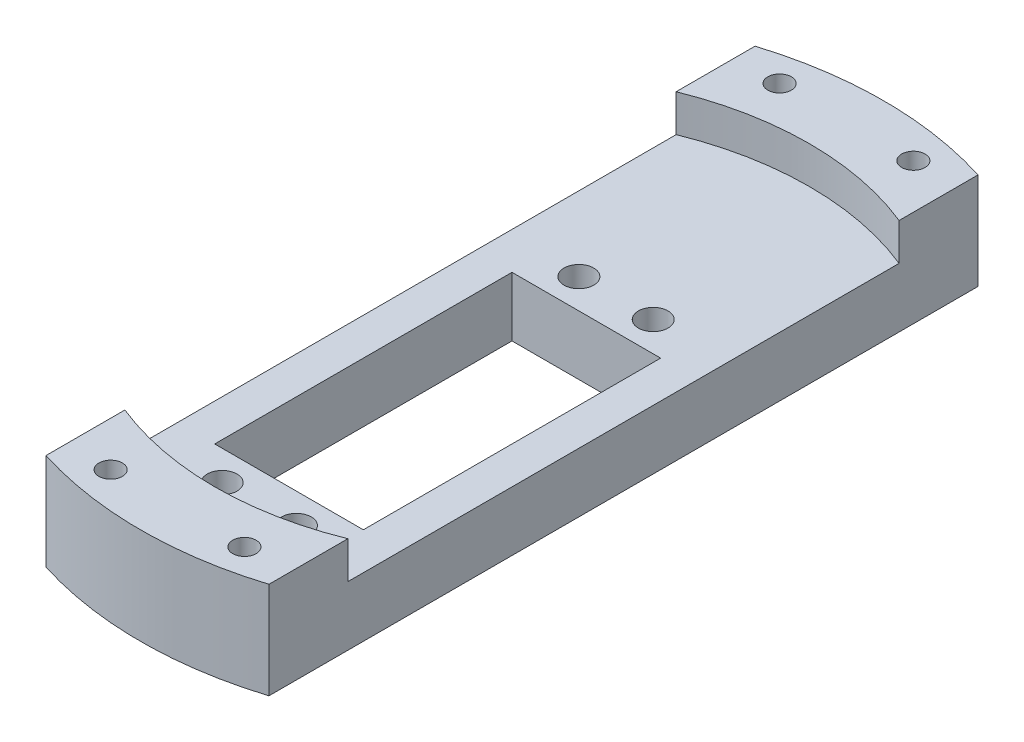
SolidWorks part; units mm, degrees
ref_plane "Спереди" through (0, 0, 0) normal (0, 0, 1) x (1, 0, 0)
ref_plane "Сверху" through (0, 0, 0) normal (0, 1, 0) x (1, 0, 0)
ref_plane "Справа" through (0, 0, 0) normal (1, 0, 0) x (0, 0, -1)
sketch "Эскиз1" plane through (0, 0, 0) normal (0, 1, 0) x (1, 0, 0)
  line L0 (0, 0) -> (0, -69.818) construction
  line L1 (-1000, -10) -> (49000, -10) construction
  line L2 (-10, -30) -> (10, -30)
  line L3 (-10, -30) -> (-10, 10)
  line L4 (-10, 10) -> (10, 10)
  line L5 (10, -30) -> (10, 10)
  line L6 (-10, -30) -> (10, 10) construction
  line L7 (-10, 10) -> (10, -30) construction
  line L8 (-1000, 0) -> (49000, 0) construction
  line L9 (-15, -47.697) -> (-15, 47.697)
  line L10 (15, -47.697) -> (15, 47.697)
  arc A0 (-15, -47.697) -> (15, -47.697) centre (0, 0) ccw
  circle A1 centre (-5, -34) radius 2
  circle A2 centre (5, -34) radius 2
  circle A3 centre (5, 14) radius 2
  circle A4 centre (-5, 14) radius 2
  arc A5 (15, 47.697) -> (-15, 47.697) centre (0, 0) ccw
  point P3 (0, -10)
  dimension "D1" = 100
  dimension "D5" = 4
  dimension "D2" = 10
  dimension "D3" = 40
  dimension "D4" = 20
  dimension "D6" = 24
  dimension "D7" = 5
  dimension "D8" = 15
  dimension "D9" = 15
extrude "Бобышка-Вытянуть1" add sketch "Эскиз1" along normal blind 8
sketch "Эскиз2" plane through (0, 8, 0) normal (0, 1, 0) x (1, 0, 0)
  line L0 (-15, 37.081) -> (-15, 47.697)
  line L1 (-15, 47.697) -> (-15, -47.697) construction
  line L2 (15, 47.697) -> (15, 37.081)
  line L3 (15, -47.697) -> (15, 47.697) construction
  line L4 (-15, -37.081) -> (-15, -47.697)
  line L5 (15, -37.081) -> (15, -47.697)
  arc A0 (-15, -47.697) -> (15, -47.697) centre (0, 0) ccw
  arc A1 (-15, -37.081) -> (15, -37.081) centre (0, 0) ccw
  arc A2 (15, 37.081) -> (-15, 37.081) centre (0, 0) ccw
  arc A3 (15, 47.697) -> (-15, 47.697) centre (0, 0) ccw
  dimension "D1" = 30
  dimension "D2" = 80
  dimension "D3" = 50
extrude "Бобышка-Вытянуть2" add sketch "Эскиз2" along normal blind 5
hole_wizard "Сверло под метчик  спиральное M31" positions "Эскиз6" profile "Эскиз7" hole size "M3x0.5" standard "DIN" end condition through all
sketch "Эскиз6" plane through (0, 13, 0) normal (0, 1, 0) x (1, 0, 0)
  point P0 (-9, -45)
  dimension "D1" = 9
  dimension "D2" = 45
sketch "Эскиз7" plane through (-9, 13, 45) normal (1, 0, 0) x (0, 0, 1)
  line L0 (0, 0) -> (0, 13)
  line L1 (0, 13) -> (1.575, 13)
  line L2 (1.575, 13) -> (1.575, 0)
  line L5 (1.575, 0) -> (0, 0)
  line L11 (0, -6.35) -> (0, 107.95) construction
  dimension "Диаметр сквозного отверстия" = 3.15
  dimension "Глубина сквозного отверстия" = 13
sketch "Эскиз8" plane through (0, 0, 0) normal (0, 1, 0) x (1, 0, 0)
  line L0 (0, 0) -> (33.0205, 0) construction
  line L1 (0, 0) -> (0, -18.8534) construction
pattern_linear "Линейный массив1" count 2 spacing 18 along (1, 0, 0) count 2 spacing 90 along (0, 0, -1) of "Сверло под метчик  спиральное M31"
